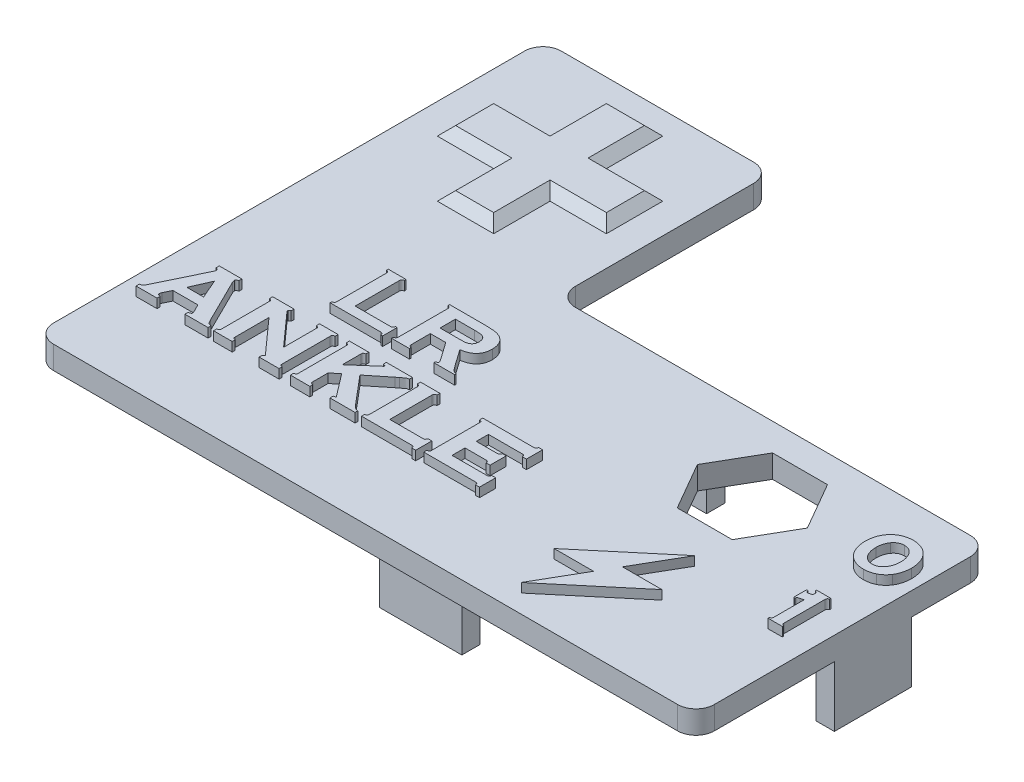
SolidWorks part; units mm, degrees
ref_plane "Front" through (0, 0, 0) normal (0, 0, 1) x (1, 0, 0)
ref_plane "Top" through (0, 0, 0) normal (0, 1, 0) x (1, 0, 0)
ref_plane "Right" through (0, 0, 0) normal (1, 0, 0) x (0, 0, -1)
sketch "Sketch1" plane through (0, 0, 0) normal (0, 1, 0) x (1, 0, 0)
  line L0 (-36.05, 15.975) -> (-36.05, 39.425)
  line L1 (-36.05, -15.975) -> (36.05, -15.975)
  line L2 (-36.05, -15.975) -> (-36.05, 15.975)
  line L3 (-11.05, 15.975) -> (36.05, 15.975)
  line L4 (36.05, -15.975) -> (36.05, 15.975)
  line L5 (-36.05, -15.975) -> (36.05, 15.975) construction
  line L6 (-36.05, 15.975) -> (36.05, -15.975) construction
  line L7 (-36.05, 39.425) -> (-11.05, 39.425)
  line L8 (-11.05, 39.425) -> (-11.05, 15.975)
  point P0 (0, 0)
  dimension "D1" = 31.95
  dimension "D2" = 72.1
  dimension "D3" = 25
  dimension "D4" = 55.4
extrude "Boss-Extrude1" add sketch "Sketch1" along normal blind 2.5
fillet "Fillet1" radius 2 6 edges at (36.05, 1.25, -15.975) (36.05, 1.25, 15.975) (-36.05, 1.25, 15.975) (-11.05, 1.25, -15.975) (-11.05, 1.25, -39.425) (-36.05, 1.25, -39.425)
sketch "Sketch2" plane through (0, 0, 0) normal (0, -1, 0) x (1, 0, 0)
  line L0 (36.05, 13.975) -> (36.05, -13.975) construction
  line L1 (34.05, -7.525) -> (36.05, -7.525)
  line L2 (34.05, -7.525) -> (34.05, 0.875)
  line L3 (34.05, 0.875) -> (36.05, 0.875)
  line L4 (36.05, -7.525) -> (36.05, 0.875)
  line L5 (34.05, -7.525) -> (36.05, 0.875) construction
  line L6 (34.05, 0.875) -> (36.05, -7.525) construction
  line L7 (35.05, -7.575) -> (35.05, 0.925) construction
  line L8 (35.05, 0.925) -> (35.05, 15.975) construction
  line L9 (-34.05, 15.975) -> (34.05, 15.975) construction
  line L10 (34.05, -15.975) -> (-9.05, -15.975) construction
  line L11 (8.5, -14.725) -> (-0.5, -14.725)
  line L12 (8.5, -14.725) -> (8.5, -12.725)
  line L13 (8.5, -12.725) -> (-0.5, -12.725)
  line L14 (-0.5, -14.725) -> (-0.5, -12.725)
  line L15 (8.5, -14.725) -> (-0.5, -12.725) construction
  line L16 (8.5, -12.725) -> (-0.5, -14.725) construction
  line L17 (8.5, 11.975) -> (-0.5, 11.975)
  line L18 (8.5, 11.975) -> (8.5, 13.975)
  line L19 (8.5, 13.975) -> (-0.5, 13.975)
  line L20 (-0.5, 11.975) -> (-0.5, 13.975)
  line L21 (8.5, 11.975) -> (-0.5, 13.975) construction
  line L22 (8.5, 13.975) -> (-0.5, 11.975) construction
  line L23 (0, 0) -> (-50000, 0) construction
  point P0 (35.05, -3.325)
  point P7 (35.05, -3.325)
  point P13 (4, -13.725)
  point P18 (4, 12.975)
  dimension "D1" = 2
  dimension "D2" = 8.4
  dimension "D3" = 15.05
  dimension "D4" = 8.5
  dimension "D5" = 2
  dimension "D6" = 1.25
  dimension "D7" = 2
  dimension "D8" = 0.5
  dimension "D9" = 9
extrude "Boss-Extrude2" add sketch "Sketch2" along normal blind 6.6
sketch "Sketch3" plane through (0, 2.5, 0) normal (0, 1, 0) x (1, 0, 0)
  line L0 (-22.8, 2.025) -> (-7.8, 2.025) construction
  line L1 (-34.05, -6.975) -> (3.45, -6.975) construction
  line L2 (29.55, 6.025) -> (36.05, 6.025) construction
  line L9 (21.9141, -1.975) -> (19.0274, -6.975)
  line L11 (17.8726, -8.975) -> (14.9859, -13.975)
  line L12 (14.9859, -13.975) -> (23.3282, -6.975)
  line L13 (23.3282, -6.975) -> (19.0274, -6.975)
  line L14 (21.9141, -1.975) -> (13.5718, -8.975)
  line L15 (13.5718, -8.975) -> (17.8726, -8.975)
  line L16 (12.7, -15.975) -> (12.7, 0.025) construction
  line L17 (-34.05, -15.975) -> (34.05, -15.975) construction
  line L18 (12.7, 0.025) -> (24.2, 0.025) construction
  line L19 (24.2, 0.025) -> (24.2, -15.975) construction
  line L20 (24.2, -15.975) -> (12.7, -15.975) construction
  line L21 (36.05, -13.975) -> (36.05, 13.975) construction
  line L22 (21.9141, -1.975) -> (14.9859, -13.975) construction
  line L23 (-26.625, 36.925) -> (-20.475, 36.925)
  line L24 (-20.475, 36.925) -> (-20.475, 30.775)
  line L25 (-36.05, 37.425) -> (-36.05, -13.975) construction
  line L26 (-20.475, 30.775) -> (-14.325, 30.775)
  line L27 (-14.325, 30.775) -> (-14.325, 24.625)
  line L28 (-14.325, 24.625) -> (-20.475, 24.625)
  line L29 (-20.475, 24.625) -> (-20.475, 18.475)
  line L30 (-20.475, 18.475) -> (-26.625, 18.475)
  line L31 (-26.625, 18.475) -> (-26.625, 24.625)
  line L32 (-26.625, 24.625) -> (-32.775, 24.625)
  line L33 (-32.775, 24.625) -> (-32.775, 30.775)
  line L34 (-32.775, 30.775) -> (-26.625, 30.775)
  line L35 (-26.625, 30.775) -> (-26.625, 36.925)
  line L36 (-11.05, 27.7) -> (-36.05, 27.7) construction
  line L37 (-11.05, 17.975) -> (-11.05, 37.425) construction
  line L38 (-36.05, 37.425) -> (-36.05, -13.975) construction
  line L39 (-13.05, 39.425) -> (-34.05, 39.425) construction
  text T0 "<b>ANKLE</b>" font "Copperplate Gothic Bold" height 6.35
  text T1 "LR" font "Copperplate Gothic Bold" height 6.35
  text T2 "0\r\n1" font "Copperplate Gothic Bold" height in points 26
  point P18 (18.45, -7.975)
  point P19 (18.45, 0.025)
  point P20 (12.7, -7.975)
  point P38 (-32.775, 27.7)
  point P43 (-15.3, 2.025)
  point P44 (-15.3, -6.975)
  point P50 (-23.55, 36.925)
  point P51 (-23.55, 27.7)
  dimension "D1" = 40
  dimension "D2" = 20
  dimension "D3" = 2
  dimension "D4" = 5
  dimension "D5" = 11.85
  dimension "D6" = 23.35
  dimension "D7" = 2
  dimension "D8" = 6.5
  dimension "D9" = 22
  dimension "D10" = 18
  dimension "D11" = 2
  dimension "D12" = 9
  dimension "D13" = 37.5
  dimension "D14" = 15
  dimension "D15" = 2.5
extrude "Boss-Extrude3" add sketch "Sketch3" along normal blind 1
sketch "Sketch4" plane through (0, 2.5, 0) normal (0, 1, 0) x (1, 0, 0)
  line L5 (34.05, 15.975) -> (-9.05, 15.975) construction
  line L7 (18.45, 2.5827) -> (18.45, -15.975) construction
  line L9 (21.45, 2.5827) -> (24.45, 7.7788)
  line L10 (24.45, 7.7788) -> (21.45, 12.975)
  line L11 (21.45, 12.975) -> (15.45, 12.975)
  line L12 (15.45, 12.975) -> (12.45, 7.7788)
  line L13 (12.45, 7.7788) -> (15.45, 2.5827)
  line L14 (15.45, 2.5827) -> (21.45, 2.5827)
  line L15 (24.2, -15.975) -> (12.7, -15.975) construction
  circle A0 centre (18.45, 7.7788) radius 5.1962 construction
  dimension "D1" = 3
  dimension "D2" = 6
extrude "Cut-Extrude1" cut sketch "Sketch4" against normal up to vertex (2.5 mm away) up to point (34.05, 0, 15.975)
chamfer "Chamfer1" distance 1 angle 45 12 edges at (-23.55, 3.5, -36.925) (-20.475, 3.5, -33.85) (-17.4, 3.5, -30.775) (-14.325, 3.5, -27.7) (-17.4, 3.5, -24.625) (-20.475, 3.5, -21.55) (-23.55, 3.5, -18.475) (-26.625, 3.5, -21.55) (-29.7, 3.5, -24.625) (-32.775, 3.5, -27.7) (-29.7, 3.5, -30.775) (-26.625, 3.5, -33.85)
